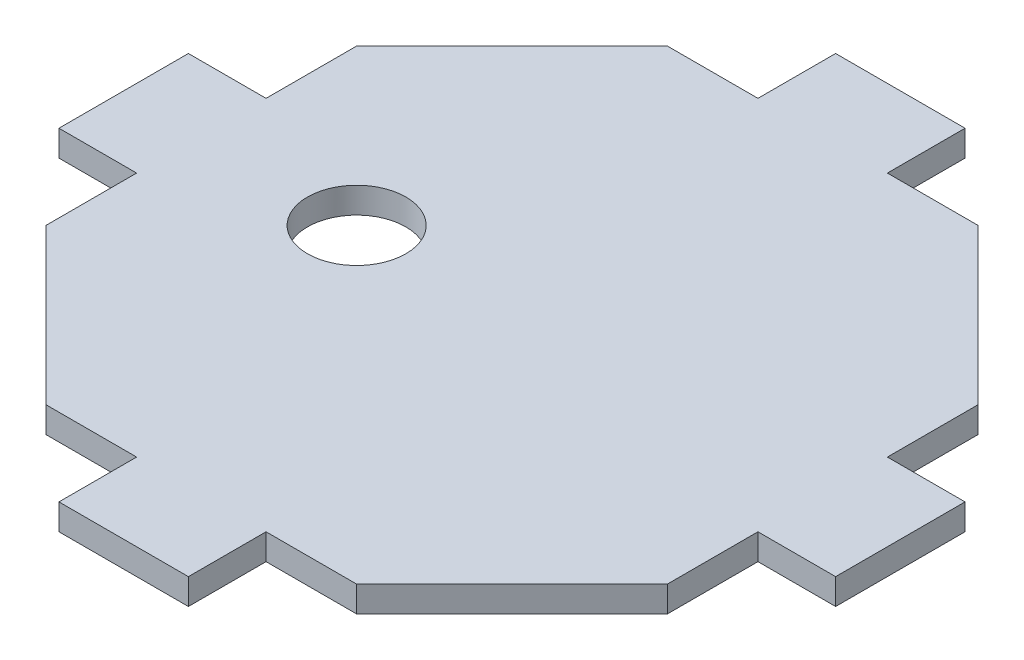
SolidWorks part; units mm, degrees
material "6061 합금"
ref_plane "정면" through (0, 0, 0) normal (0, 0, 1) x (1, 0, 0)
ref_plane "윗면" through (0, 0, 0) normal (0, 1, 0) x (1, 0, 0)
ref_plane "우측면" through (0, 0, 0) normal (1, 0, 0) x (0, 0, -1)
sketch "스케치1" plane through (0, 0, 0) normal (0, 1, 0) x (1, 0, 0)
  line L7 (39, 0) -> (-66.3, 0) construction
  line L9 (0, 39) -> (0, -39) construction
  line L14 (-30, -60) -> (30, -60)
  line L15 (30, -60) -> (60, -30)
  line L16 (60, -30) -> (60, 30)
  line L17 (60, 30) -> (30, 60)
  line L18 (30, 60) -> (-30, 60)
  line L19 (-30, 60) -> (-60, 30)
  line L20 (-60, 30) -> (-60, -30)
  line L21 (-60, -30) -> (-30, -60)
  line L22 (-60, 12.5) -> (-75, 12.5)
  line L23 (-75, 12.5) -> (-75, -12.5)
  line L24 (-75, -12.5) -> (-60, -12.5)
  line L25 (-12.5, -60) -> (-12.5, -75)
  line L26 (-12.5, -75) -> (12.5, -75)
  line L27 (12.5, -75) -> (12.5, -60)
  line L28 (60, -12.5) -> (75, -12.5)
  line L29 (75, -12.5) -> (75, 12.5)
  line L30 (75, 12.5) -> (60, 12.5)
  line L31 (-12.5, 60) -> (-12.5, 75)
  line L32 (-12.5, 75) -> (12.5, 75)
  line L33 (12.5, 75) -> (12.5, 60)
  point P0 (0, 0)
  dimension "D3" = 60
  dimension "D4" = 60
  dimension "D5" = 60
  dimension "D6" = 60
  dimension "D7" = 30
  dimension "D8" = 30
  dimension "D9" = 30
  dimension "D10" = 30
  dimension "D11" = 30
  dimension "D12" = 30
  dimension "D13" = 30
  dimension "D15" = 25
  dimension "D16" = 25
  dimension "D17" = 25
  dimension "D18" = 25
  dimension "D19" = 15
  dimension "D21" = 15
  dimension "D22" = 15
  dimension "D23" = 15
  dimension "D24" = 12.5
  dimension "D25" = 12.5
  dimension "D26" = 12.5
extrude "보스-돌출1" add sketch "스케치1" along normal blind 5 contours L18 L19 L17 | L20 L21 L19 | L23 L24 L20 L22 | L33 L32 L31 L18 | L16 L17 L15 | L29 L30 L16 L28 | L21 L14 L15 | L26 L27 L14 L25 region at (0, 0, 0) region at (0, 0, 67.5) region at (-67.5, 0, 0) region at (67.5, 0, 0) region at (0, 0, -67.5)
ref_plane "평면1" through (0, 0, 0) normal (0, -1, 0) x (-1, 0, 0)
sketch "스케치2" plane through (0, 0, 0) normal (0, -1, 0) x (-1, 0, 0)
  circle A0 centre (30, 0) radius 9.5
  dimension "D1" = 19
extrude "컷-돌출1" cut sketch "스케치2" against normal blind 10
